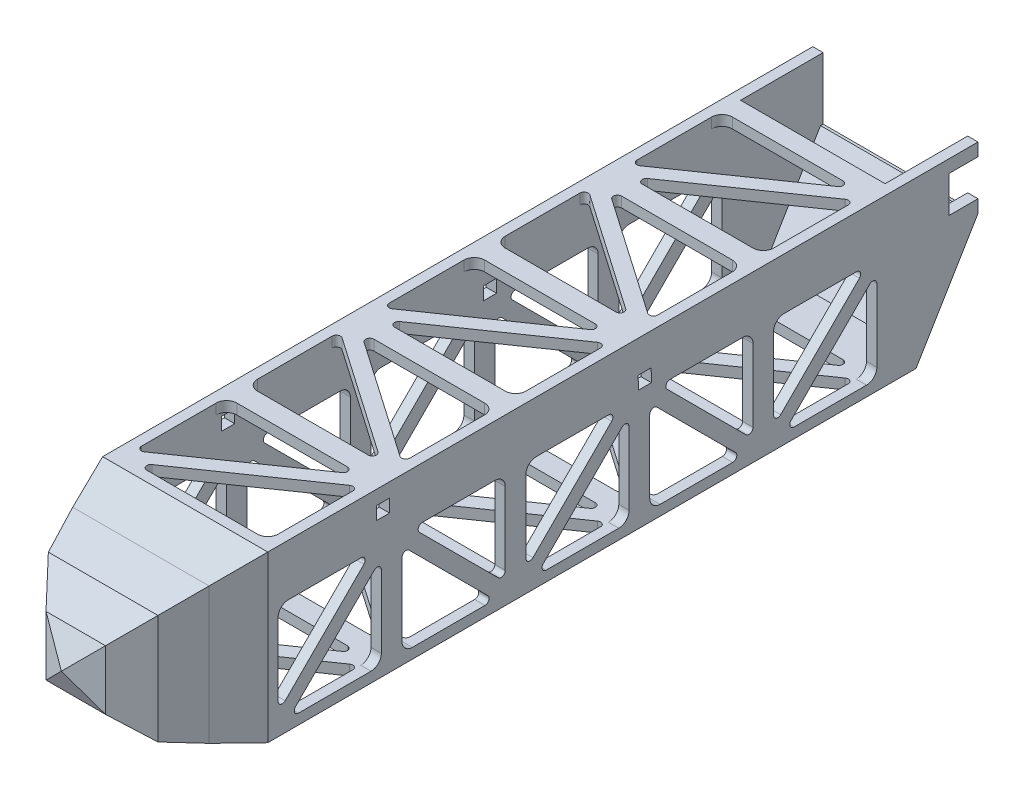
SolidWorks part; units mm, degrees
material "Balsa"
ref_plane "Front Plane" through (0, 0, 0) normal (0, 0, 1) x (1, 0, 0)
ref_plane "Top Plane" through (0, 0, 0) normal (0, 1, 0) x (1, 0, 0)
ref_plane "Right Plane" through (0, 0, 0) normal (1, 0, 0) x (0, 0, -1)
sketch "Sketch1" plane through (0, 0, 0) normal (0, 0, 1) x (1, 0, 0)
  line L1 (-50.8, -50.8) -> (50.8, -50.8)
  line L2 (-50.8, -50.8) -> (-50.8, 50.8)
  line L3 (-50.8, 50.8) -> (50.8, 50.8)
  line L4 (50.8, -50.8) -> (50.8, 50.8)
  line L5 (-50.8, -50.8) -> (50.8, 50.8) construction
  line L6 (-50.8, 50.8) -> (50.8, -50.8) construction
  point P0 (0, 0)
  dimension "D1" = 101.6
extrude "Boss-Extrude1" add sketch "Sketch1" along normal blind 436.88 contours L2 L1 L4 L3
ref_plane "Plane1" through (0, 0, 464.1566) normal (0, 0, 1) x (1, 0, 0)
sketch "Sketch3" plane through (0, 0, 464.1566) normal (0, 0, 1) x (1, 0, 0)
  line L1 (-41.9373, -41.9373) -> (41.9373, -41.9373)
  line L2 (-41.9373, -41.9373) -> (-41.9373, 41.9373)
  line L3 (-41.9373, 41.9373) -> (41.9373, 41.9373)
  line L4 (41.9373, -41.9373) -> (41.9373, 41.9373)
  line L5 (-41.9373, -41.9373) -> (41.9373, 41.9373) construction
  line L6 (-41.9373, 41.9373) -> (41.9373, -41.9373) construction
  point P0 (0, 0)
  dimension "D1" = 83.8746
  dimension "D2" = 83.8746
sketch "Sketch5" plane through (0, 0, 436.88) normal (0, 0, 1) x (1, 0, 0)
  line L0 (50.8, -50.8) -> (50.8, 50.8) construction
  line L1 (-50.8, 50.8) -> (50.8, 50.8) construction
  line L2 (-50.8, -50.8) -> (-50.8, 50.8) construction
  line L3 (-50.8, -50.8) -> (50.8, -50.8) construction
  line L4 (50.8, -50.8) -> (50.8, 50.8)
  line L5 (-50.8, 50.8) -> (50.8, 50.8)
  line L6 (-50.8, -50.8) -> (-50.8, 50.8)
  line L7 (-50.8, -50.8) -> (50.8, -50.8)
  dimension "D1" = 101.6
  dimension "D2" = 101.6
loft "Loft2" add profiles "Sketch5", "Sketch3" connector at (-50.8, 50.8, 436.88) connector at (-41.9373, 41.9373, 464.1566)
ref_plane "Plane2" through (0, 0, 487.3594) normal (0, 0, 1) x (1, 0, 0)
sketch "Sketch6" plane through (0, 0, 487.3594) normal (0, 0, 1) x (1, 0, 0)
  line L1 (-33.716, -33.716) -> (33.716, -33.716)
  line L2 (-33.716, -33.716) -> (-33.716, 33.716)
  line L3 (-33.716, 33.716) -> (33.716, 33.716)
  line L4 (33.716, -33.716) -> (33.716, 33.716)
  line L5 (-33.716, -33.716) -> (33.716, 33.716) construction
  line L6 (-33.716, 33.716) -> (33.716, -33.716) construction
  point P0 (0, 0)
loft "Loft3" add profiles "Sketch3<6>", "Sketch6" connector at (-41.9373, 41.9373, 464.1566) connector at (-33.716, 33.716, 487.3594)
sketch "Sketch3<6>" plane through (0, 0, 464.1566) normal (0, 0, 1) x (1, 0, 0) same geometry as "Sketch3"
ref_plane "Plane3" through (0, 0, 504.2173) normal (0, 0, 1) x (1, 0, 0)
sketch "Sketch7" plane through (0, 0, 504.2173) normal (0, 0, 1) x (1, 0, 0)
  line L5 (-41.9373, -41.9373) -> (41.9373, 41.9373) construction
  line L6 (-18.3041, -18.3041) -> (18.3041, -18.3041)
  line L8 (-18.3041, -18.3041) -> (-18.3041, 18.3041)
  line L9 (-18.3041, 18.3041) -> (18.3041, 18.3041)
  line L10 (18.3041, -18.3041) -> (18.3041, 18.3041)
  line L11 (-18.3041, -18.3041) -> (18.3041, 18.3041) construction
  line L12 (-18.3041, 18.3041) -> (18.3041, -18.3041) construction
  point P1 (0, 0)
loft "Loft4" add profiles "Sketch6<4>", "Sketch7" connector at (33.716, 33.716, 487.3594) connector at (18.3041, 18.3041, 504.2173)
sketch "Sketch6<4>" plane through (0, 0, 487.3594) normal (0, 0, 1) x (1, 0, 0) same geometry as "Sketch6"
sketch3d "3DSketch1" plane through (0, 0, 0) normal (0, 0, 1) x (1, 0, 0)
  dimension "D1" = 8.8627
sketch "Sketch8" plane through (0, 0, 513.08) normal (0, 0, 1) x (1, 0, 0)
  point P0 (0, 0)
loft "Loft5" add profiles "Sketch8", "Sketch7<5>"
sketch "Sketch7<5>" plane through (0, 0, 504.2173) normal (0, 0, 1) x (1, 0, 0) same geometry as "Sketch7"
shell "Shell1" thickness 6.35 removed face at (0, 0, 0)
sketch "Sketch10" plane through (50.8, 0, 0) normal (1, 0, 0) x (0, 0, -1)
  line L0 (-436.88, 50.8) -> (0, 50.8) construction
  line L3 (0, 50.8) -> (-68.9584, 50.8)
  line L4 (-68.9584, -50.8) -> (-68.9584, 50.8)
  line L5 (0, 50.8) -> (0, 12.7)
  line L6 (0, -50.8) -> (-38.1, -50.8)
  line L7 (0, 12.7) -> (-38.1, -50.8)
  line L8 (0, 12.7) -> (0, -50.8)
  line M16 (0, -50.8) -> (0, 50.8)
  line M19 (-436.88, -50.8) -> (0, -50.8)
  dimension "D1" = 38.1
  dimension "D2" = 38.1
  dimension "D3" = 63.5
extrude "Cut-Extrude2" cut sketch "Sketch10" against normal through all contours L7 M16 M19 region at (50.8, -29.6333, 12.7)
sketch "Sketch11" plane through (50.8, 0, 0) normal (1, 0, 0) x (0, 0, -1)
  line L0 (-38.1, -50.8) -> (-39.6875, -50.8)
  line L1 (-436.88, -50.8) -> (-38.1, -50.8) construction
  line L2 (0, 50.8) -> (-1.5875, 50.8)
  line L3 (-436.88, 50.8) -> (0, 50.8) construction
  line L4 (-1.5875, 50.8) -> (-1.5875, 12.7)
  line L5 (0, 50.8) -> (0, 12.7)
  line L6 (-1.5875, 12.7) -> (-39.6875, -50.8)
  line L7 (0, 12.7) -> (-38.1, -50.8)
  dimension "D1" = 1.5875
  dimension "D2" = 1.5875
extrude "Boss-Extrude2" add sketch "Sketch11" against normal blind 101.6
sketch "Sketch12" plane through (0, 0, 0) normal (0, 0, -1) x (-1, 0, 0)
  line L0 (-50.8, 50.8) -> (-44.45, 50.8)
  line L1 (50.8, 50.8) -> (-50.8, 50.8) construction
  line L2 (50.8, 12.7) -> (-50.8, 12.7) construction
  line L3 (-44.45, 50.8) -> (44.45, 50.8)
  line L4 (-44.45, 50.8) -> (-44.45, 12.7)
  line L5 (-44.45, 12.7) -> (44.45, 12.7)
  line L6 (44.45, 50.8) -> (44.45, 12.7)
  line M7 (-50.8, 12.7) -> (50.8, 12.7)
  line M9 (50.8, 50.8) -> (-50.8, 50.8)
  dimension "D1" = 6.35
  dimension "D2" = 88.9
extrude "Cut-Extrude3" cut sketch "Sketch12" against normal blind 50.8 contours L6 L4 M9 M7 region at (0, 31.75, 0)
sketch "Sketch15" plane through (50.8, 0, 0) normal (1, 0, 0) x (0, 0, -1)
  line L0 (0, 12.7) -> (0, 50.8) construction
  line L1 (0, 42.926) -> (-17.78, 42.926)
  line L2 (0, 42.926) -> (0, 20.574)
  line L3 (0, 20.574) -> (-17.78, 20.574)
  line L4 (-17.78, 42.926) -> (-17.78, 20.574)
  line L5 (-436.88, 50.8) -> (0, 50.8) construction
  dimension "D1" = 17.78
  dimension "D2" = 22.352
  dimension "D3" = 7.874
extrude "Cut-Extrude5" cut sketch "Sketch15" against normal up to surface (6.35 mm away)
sketch "Sketch16" plane through (50.8, 0, 0) normal (1, 0, 0) x (0, 0, -1)
  line L0 (-436.88, -50.8) -> (-436.88, 50.8) construction
  line L1 (-424.18, 19.05) -> (-379.5121, 19.05)
  line L2 (-430.53, 12.7) -> (-430.53, -31.9679)
  line L3 (-418.0479, -44.45) -> (-373.38, -44.45)
  line L4 (-367.03, 6.5679) -> (-367.03, -38.1)
  line L5 (-436.88, -50.8) -> (-38.1, -50.8) construction
  line L6 (-354.33, 6.5679) -> (-354.33, -38.1)
  line L7 (-341.8479, 19.05) -> (-297.18, 19.05)
  line L8 (-290.83, 12.7) -> (-290.83, -31.9679)
  line L9 (-347.98, -44.45) -> (-303.3121, -44.45)
  line L10 (-278.13, 12.7) -> (-278.13, -31.9679)
  line L11 (-271.78, 19.05) -> (-227.1121, 19.05)
  line L12 (-214.63, 6.5679) -> (-214.63, -38.1)
  line L13 (-265.6479, -44.45) -> (-220.98, -44.45)
  line L14 (-201.93, 6.5679) -> (-201.93, -38.1)
  line L15 (-189.4479, 19.05) -> (-144.78, 19.05)
  line L16 (-138.43, 12.7) -> (-138.43, -31.9679)
  line L17 (-195.58, -44.45) -> (-150.9121, -44.45)
  line L18 (-125.73, 12.7) -> (-125.73, -31.9679)
  line L19 (-119.38, 19.05) -> (-74.7121, 19.05)
  line L20 (-62.23, 6.5679) -> (-62.23, -38.1)
  line L21 (-113.2479, -44.45) -> (-68.58, -44.45)
  line L22 (-377.7161, 14.7139) -> (-426.1939, -33.7639)
  line L23 (-419.8439, -40.1139) -> (-371.3661, 8.3639)
  line L24 (-349.9939, 8.3639) -> (-301.5161, -40.1139)
  line L25 (-343.6439, 14.7139) -> (-295.1661, -33.7639)
  line L26 (-273.7939, -33.7639) -> (-225.3161, 14.7139)
  line L27 (-218.9661, 8.3639) -> (-267.4439, -40.1139)
  line L28 (-197.5939, 8.3639) -> (-149.1161, -40.1139)
  line L29 (-142.7661, -33.7639) -> (-191.2439, 14.7139)
  line L30 (-121.3939, -33.7639) -> (-72.9161, 14.7139)
  line L31 (-66.5661, 8.3639) -> (-115.0439, -40.1139)
  arc A0 (-430.53, -38.1) -> (-424.18, -44.45) centre (-424.18, -38.1) ccw
  arc A1 (-373.38, -44.45) -> (-367.03, -38.1) centre (-373.38, -38.1) ccw
  arc A2 (-373.38, 19.05) -> (-367.03, 12.7) centre (-373.38, 12.7) cw
  arc A3 (-424.18, 19.05) -> (-430.53, 12.7) centre (-424.18, 12.7) ccw
  arc A4 (-347.98, 19.05) -> (-354.33, 12.7) centre (-347.98, 12.7) ccw
  arc A5 (-354.33, -38.1) -> (-347.98, -44.45) centre (-347.98, -38.1) ccw
  arc A6 (-297.18, 19.05) -> (-290.83, 12.7) centre (-297.18, 12.7) cw
  arc A7 (-297.18, -44.45) -> (-290.83, -38.1) centre (-297.18, -38.1) ccw
  arc A8 (-271.78, 19.05) -> (-278.13, 12.7) centre (-271.78, 12.7) ccw
  arc A9 (-278.13, -38.1) -> (-271.78, -44.45) centre (-271.78, -38.1) ccw
  arc A10 (-220.98, 19.05) -> (-214.63, 12.7) centre (-220.98, 12.7) cw
  arc A11 (-220.98, -44.45) -> (-214.63, -38.1) centre (-220.98, -38.1) ccw
  arc A12 (-195.58, 19.05) -> (-201.93, 12.7) centre (-195.58, 12.7) ccw
  arc A13 (-201.93, -38.1) -> (-195.58, -44.45) centre (-195.58, -38.1) ccw
  arc A14 (-144.78, 19.05) -> (-138.43, 12.7) centre (-144.78, 12.7) cw
  arc A15 (-144.78, -44.45) -> (-138.43, -38.1) centre (-144.78, -38.1) ccw
  arc A16 (-119.38, 19.05) -> (-125.73, 12.7) centre (-119.38, 12.7) ccw
  arc A17 (-125.73, -38.1) -> (-119.38, -44.45) centre (-119.38, -38.1) ccw
  arc A18 (-68.58, 19.05) -> (-62.23, 12.7) centre (-68.58, 12.7) cw
  arc A19 (-68.58, -44.45) -> (-62.23, -38.1) centre (-68.58, -38.1) ccw
  arc A20 (-74.7121, 19.05) -> (-72.9161, 14.7139) centre (-74.7121, 16.51) cw
  arc A21 (-66.5661, 8.3639) -> (-62.23, 6.5679) centre (-64.77, 6.5679) cw
  arc A22 (-115.0439, -40.1139) -> (-113.2479, -44.45) centre (-113.2479, -41.91) ccw
  arc A23 (-121.3939, -33.7639) -> (-125.73, -31.9679) centre (-123.19, -31.9679) cw
  arc A24 (-150.9121, -44.45) -> (-149.1161, -40.1139) centre (-150.9121, -41.91) ccw
  arc A25 (-142.7661, -33.7639) -> (-138.43, -31.9679) centre (-140.97, -31.9679) ccw
  arc A26 (-189.4479, 19.05) -> (-191.2439, 14.7139) centre (-189.4479, 16.51) ccw
  arc A27 (-197.5939, 8.3639) -> (-201.93, 6.5679) centre (-199.39, 6.5679) ccw
  arc A28 (-227.1121, 19.05) -> (-225.3161, 14.7139) centre (-227.1121, 16.51) cw
  arc A29 (-218.9661, 8.3639) -> (-214.63, 6.5679) centre (-217.17, 6.5679) cw
  arc A30 (-265.6479, -44.45) -> (-267.4439, -40.1139) centre (-265.6479, -41.91) cw
  arc A31 (-278.13, -31.9679) -> (-273.7939, -33.7639) centre (-275.59, -31.9679) ccw
  arc A32 (-303.3121, -44.45) -> (-301.5161, -40.1139) centre (-303.3121, -41.91) ccw
  arc A33 (-290.83, -31.9679) -> (-295.1661, -33.7639) centre (-293.37, -31.9679) cw
  arc A34 (-341.8479, 19.05) -> (-343.6439, 14.7139) centre (-341.8479, 16.51) ccw
  arc A35 (-349.9939, 8.3639) -> (-354.33, 6.5679) centre (-351.79, 6.5679) ccw
  arc A36 (-367.03, 6.5679) -> (-371.3661, 8.3639) centre (-369.57, 6.5679) ccw
  arc A37 (-418.0479, -44.45) -> (-419.8439, -40.1139) centre (-418.0479, -41.91) cw
  arc A38 (-377.7161, 14.7139) -> (-379.5121, 19.05) centre (-379.5121, 16.51) ccw
  arc A39 (-426.1939, -33.7639) -> (-430.53, -31.9679) centre (-427.99, -31.9679) cw
  point P12 (-367.03, -44.45)
  point P15 (-367.03, 19.05)
  point P18 (-430.53, 19.05)
  dimension "D1" = 6.35
  dimension "D5" = 6.35
  dimension "D7" = 2.54
  dimension "D2" = 6.35
  dimension "D3" = 63.5
  dimension "D4" = 63.5
  dimension "D6" = 5
extrude "Cut-Extrude6" cut sketch "Sketch16" against normal up to surface (101.6 mm away) contours L1 A3 L2 L22 | L3 A1 L4 L23 | L6 A5 L9 L24 | A6 L7 L25 L8 | L11 A8 L10 L26 | L13 A11 L12 L27 | L14 A13 L17 L28 | A14 L15 L29 L16 | L21 A19 L20 L31 | L19 A16 L18 L30 region at (50.8, -0.0083, 411.4717) region at (50.8, -25.3917, 386.0883) region at (50.8, -25.3917, 335.2717) region at (50.8, -0.0083, 309.8883) region at (50.8, -0.0083, 259.0717) region at (50.8, -25.3917, 233.6883) region at (50.8, -25.3917, 182.8717) region at (50.8, -0.0083, 157.4883) region at (50.8, -0.0083, 106.6717) region at (50.8, -25.3917, 81.2883) up to face at (-50.8, 2.54, 182.372)
sketch "Sketch17" plane through (0, 50.8, 0) normal (0, 1, 0) x (1, 0, 0)
  line L0 (50.8, -436.88) -> (50.8, 0) construction
  line L1 (38.1, -430.53) -> (-22.2093, -430.53)
  line L2 (44.45, -424.18) -> (44.45, -382.8539)
  line L3 (22.2093, -367.03) -> (-38.1, -367.03)
  line L4 (-44.45, -414.7061) -> (-44.45, -373.38)
  line L5 (-50.8, -436.88) -> (50.8, -436.88) construction
  line L6 (-50.8, -436.88) -> (-50.8, 0) construction
  line L7 (44.45, -344.747) -> (44.45, -303.4209)
  line L8 (22.2093, -360.5709) -> (-38.1, -360.5709)
  line L9 (-44.45, -354.2209) -> (-44.45, -306.6045)
  line L11 (44.45, -284.2618) -> (44.45, -236.6454)
  line L12 (38.1, -290.6118) -> (-32.7601, -290.6118)
  line L13 (-44.45, -281.0782) -> (-44.45, -233.4618)
  line L14 (37.5789, -227.1118) -> (-38.1, -227.1118)
  line L15 (44.45, -211.1191) -> (44.45, -163.5027)
  line L16 (32.7601, -220.6527) -> (-38.1, -220.6527)
  line L17 (-44.45, -214.3027) -> (-44.45, -166.6863)
  line L19 (44.45, -144.3436) -> (44.45, -98.3913)
  line L20 (38.1, -150.6936) -> (-37.3066, -150.6936)
  line L21 (-44.45, -139.4958) -> (-44.45, -93.5436)
  line L22 (29.9688, -87.1936) -> (-38.1, -87.1936)
  line L23 (-36.6606, -418.7874) -> (25.0348, -376.0751)
  line L24 (38.1, -367.03) -> (44.45, -373.38)
  line L25 (-25.0348, -421.4849) -> (36.6606, -378.7726)
  line L26 (36.6606, -348.8283) -> (-31.4146, -301.6993)
  line L27 (-41.8325, -305.233) -> (25.0348, -351.5257)
  line L28 (-33.7096, -287.5723) -> (41.8325, -235.2739)
  line L29 (38.5284, -226.8152) -> (-41.8325, -282.4497)
  line L30 (33.7096, -217.6132) -> (-41.8325, -165.3148)
  line L31 (-31.4146, -161.7811) -> (41.8325, -212.4906)
  line L32 (-38.7524, -151.1452) -> (40.4642, -96.303)
  line L33 (31.4146, -91.822) -> (-40.4642, -141.5842)
  line L35 (38.1, -157.1527) -> (-37.3066, -157.1527) [skipped]
  line L36 (38.1, -157.1527) -> (35.6588, -123.3001)
  line L37 (-29.9688, -157.1527) -> (38.1, -157.1527)
  line L38 (-29.9688, -297.0709) -> (38.1, -297.0709)
  line L39 (38.1, -297.0709) -> (-36.5494, -297.0709) [skipped]
  arc A0 (44.45, -373.38) -> (38.1, -367.03) centre (38.1, -373.38) ccw
  arc A1 (38.1, -430.53) -> (44.45, -424.18) centre (38.1, -424.18) ccw
  arc A2 (-38.1, -430.53) -> (-44.45, -424.18) centre (-38.1, -424.18) cw
  arc A3 (-38.1, -367.03) -> (-44.45, -373.38) centre (-38.1, -373.38) ccw
  arc A4 (38.1, -360.5709) -> (44.45, -354.2209) centre (38.1, -354.2209) ccw
  arc A5 (44.45, -303.4209) -> (38.1, -297.0709) centre (38.1, -303.4209) ccw
  arc A6 (-38.1, -360.5709) -> (-44.45, -354.2209) centre (-38.1, -354.2209) cw
  arc A7 (-38.1, -297.0709) -> (-44.45, -303.4209) centre (-38.1, -303.4209) ccw
  arc A8 (38.1, -290.6118) -> (44.45, -284.2618) centre (38.1, -284.2618) ccw
  arc A9 (44.45, -233.4618) -> (38.1, -227.1118) centre (38.1, -233.4618) ccw
  arc A10 (-38.1, -290.6118) -> (-44.45, -284.2618) centre (-38.1, -284.2618) cw
  arc A11 (-38.1, -227.1118) -> (-44.45, -233.4618) centre (-38.1, -233.4618) ccw
  arc A12 (38.1, -220.6527) -> (44.45, -214.3027) centre (38.1, -214.3027) ccw
  arc A13 (44.45, -163.5027) -> (38.1, -157.1527) centre (38.1, -163.5027) ccw
  arc A14 (-38.1, -220.6527) -> (-44.45, -214.3027) centre (-38.1, -214.3027) cw
  arc A16 (38.1, -150.6936) -> (44.45, -144.3436) centre (38.1, -144.3436) ccw
  arc A17 (44.45, -93.5436) -> (38.1, -87.1936) centre (38.1, -93.5436) ccw
  arc A18 (-38.1, -150.6936) -> (-44.45, -144.3436) centre (-38.1, -144.3436) cw
  arc A19 (-38.1, -87.1936) -> (-44.45, -93.5436) centre (-38.1, -93.5436) ccw
  arc A20 (-40.4642, -141.5842) -> (-44.45, -139.4958) centre (-41.91, -139.4958) cw
  arc A21 (31.4146, -91.822) -> (29.9688, -87.1936) centre (29.9688, -89.7336) ccw
  arc A22 (40.4642, -96.303) -> (44.45, -98.3913) centre (41.91, -98.3913) cw
  arc A23 (-38.7524, -151.1452) -> (-37.3066, -150.6936) centre (-37.3066, -153.2336) ccw
  arc A25 (-41.8325, -165.3148) -> (-44.45, -166.6863) centre (-42.7819, -166.6863) ccw
  arc A26 (44.45, -211.1191) -> (41.8325, -212.4906) centre (42.7819, -211.1191) cw
  arc A27 (33.7096, -217.6132) -> (32.7601, -220.6527) centre (32.7601, -218.9846) cw
  arc A28 (37.5789, -227.1118) -> (38.5284, -226.8152) centre (37.5789, -225.4437) cw
  arc A29 (41.8325, -235.2739) -> (44.45, -236.6454) centre (42.7819, -236.6454) cw
  arc A30 (-32.7601, -290.6118) -> (-33.7096, -287.5723) centre (-32.7601, -288.9437) cw
  arc A31 (-41.8325, -282.4497) -> (-44.45, -281.0782) centre (-42.7819, -281.0782) cw
  arc A32 (-44.45, -306.6045) -> (-41.8325, -305.233) centre (-42.7819, -306.6045) cw
  arc A34 (44.45, -344.747) -> (36.6606, -348.8283) centre (39.4861, -344.747) cw
  arc A35 (22.2093, -360.5709) -> (25.0348, -351.5257) centre (22.2093, -355.607) ccw
  arc A36 (44.45, -382.8539) -> (36.6606, -378.7726) centre (39.4861, -382.8539) ccw
  arc A37 (25.0348, -376.0751) -> (22.2093, -367.03) centre (22.2093, -371.9939) ccw
  arc A38 (-44.45, -414.7061) -> (-36.6606, -418.7874) centre (-39.4861, -414.7061) ccw
  arc A39 (-22.2093, -430.53) -> (-25.0348, -421.4849) centre (-22.2093, -425.5661) cw
  arc A40 (-38.1, -157.1527) -> (-44.45, -163.5027) centre (-38.1, -163.5027) ccw [skipped]
  arc A41 (-31.4146, -161.7811) -> (-29.9688, -157.1527) centre (-29.9688, -159.6927) cw
  arc A42 (-31.4146, -301.6993) -> (-29.9688, -297.0709) centre (-29.9688, -299.6109) cw
  point P16 (-44.45, -430.53)
  point P19 (-44.45, -367.03)
  dimension "D1" = 6.35
  dimension "D5" = 6.35
  dimension "D7" = 2.54
  dimension "D2" = 6.35
  dimension "D4" = 63.5
  dimension "D6" = 5
  dimension "D8" = 2.54
  dimension "D9" = 2.54
  dimension "D3" = 6.35
sketch "Sketch18" plane through (0, 50.8, 0) normal (0, 1, 0) x (1, 0, 0)
  line L0 (-50.8, -436.88) -> (-50.8, 0) construction
  line L1 (38.1, -430.53) -> (-29.9688, -430.53)
  line L2 (44.45, -424.18) -> (44.45, -378.2278)
  line L3 (29.9688, -367.03) -> (-38.1, -367.03)
  line L4 (-44.45, -419.3322) -> (-44.45, -373.38)
  line L5 (50.8, -436.88) -> (50.8, 0) construction
  line L6 (-50.8, -436.88) -> (50.8, -436.88) construction
  line L7 (-40.4642, -299.9394) -> (31.4146, -349.7016)
  line L8 (-38.1, -354.33) -> (29.9688, -354.33)
  line L9 (-44.45, -347.98) -> (-44.45, -302.0278)
  line L10 (-29.9688, -290.83) -> (38.1, -290.83)
  line L11 (44.45, -343.1322) -> (44.45, -297.18)
  line L12 (40.4642, -345.2206) -> (-31.4146, -295.4584)
  line L13 (31.4146, -371.6584) -> (-40.4642, -421.4206)
  line L14 (-31.4146, -425.9016) -> (40.4642, -376.1394)
  line L15 (38.1, -278.13) -> (-29.9688, -278.13)
  line L16 (44.45, -271.78) -> (44.45, -225.8278)
  line L17 (-31.4146, -273.5016) -> (40.4642, -223.7394)
  line L18 (31.4146, -219.2584) -> (-40.4642, -269.0206)
  line L19 (29.9688, -214.63) -> (-38.1, -214.63)
  line L20 (-44.45, -266.9322) -> (-44.45, -220.98)
  line L21 (-38.1, -201.93) -> (29.9688, -201.93)
  line L22 (-44.45, -195.58) -> (-44.45, -149.6278)
  line L23 (-40.4642, -147.5394) -> (31.4146, -197.3016)
  line L24 (40.4642, -192.8206) -> (-31.4146, -143.0584)
  line L25 (-29.9688, -138.43) -> (38.1, -138.43)
  line L26 (44.45, -190.7322) -> (44.45, -144.78)
  line L27 (38.1, -125.73) -> (-29.9688, -125.73)
  line L28 (44.45, -119.38) -> (44.45, -73.4278)
  line L29 (-31.4146, -121.1016) -> (40.4642, -71.3394)
  line L30 (31.4146, -66.8584) -> (-40.4642, -116.6206)
  line L31 (29.9688, -62.23) -> (-38.1, -62.23)
  line L32 (-44.45, -114.5322) -> (-44.45, -68.58)
  line L39 (-38.1, -49.53) -> (29.9688, -49.53) [skipped]
  line L40 (-40.4642, 4.8606) -> (31.4146, -44.9016) [skipped]
  line L41 (-44.45, -43.18) -> (-44.45, 2.7722) [skipped]
  line L42 (40.4642, -40.4206) -> (-31.4146, 9.3416) [skipped]
  line L43 (-29.9688, 13.97) -> (38.1, 13.97) [skipped]
  line L44 (44.45, -38.3322) -> (44.45, 7.62) [skipped]
  arc A0 (38.1, -430.53) -> (44.45, -424.18) centre (38.1, -424.18) ccw
  arc A3 (-38.1, -367.03) -> (-44.45, -373.38) centre (-38.1, -373.38) ccw
  arc A4 (-38.1, -354.33) -> (-44.45, -347.98) centre (-38.1, -347.98) cw
  arc A6 (38.1, -290.83) -> (44.45, -297.18) centre (38.1, -297.18) cw
  arc A8 (44.45, -343.1322) -> (40.4642, -345.2206) centre (41.91, -343.1322) cw
  arc A9 (-29.9688, -290.83) -> (-31.4146, -295.4584) centre (-29.9688, -293.37) ccw
  arc A10 (-44.45, -302.0278) -> (-40.4642, -299.9394) centre (-41.91, -302.0278) cw
  arc A11 (29.9688, -354.33) -> (31.4146, -349.7016) centre (29.9688, -351.79) ccw
  arc A12 (44.45, -378.2278) -> (40.4642, -376.1394) centre (41.91, -378.2278) ccw
  arc A13 (29.9688, -367.03) -> (31.4146, -371.6584) centre (29.9688, -369.57) cw
  arc A14 (-29.9688, -430.53) -> (-31.4146, -425.9016) centre (-29.9688, -427.99) cw
  arc A15 (-44.45, -419.3322) -> (-40.4642, -421.4206) centre (-41.91, -419.3322) ccw
  arc A16 (-29.9688, -278.13) -> (-31.4146, -273.5016) centre (-29.9688, -275.59) cw
  arc A17 (38.1, -278.13) -> (44.45, -271.78) centre (38.1, -271.78) ccw
  arc A18 (44.45, -225.8278) -> (40.4642, -223.7394) centre (41.91, -225.8278) ccw
  arc A19 (-44.45, -266.9322) -> (-40.4642, -269.0206) centre (-41.91, -266.9322) ccw
  arc A20 (29.9688, -214.63) -> (31.4146, -219.2584) centre (29.9688, -217.17) cw
  arc A21 (-38.1, -214.63) -> (-44.45, -220.98) centre (-38.1, -220.98) ccw
  arc A22 (29.9688, -201.93) -> (31.4146, -197.3016) centre (29.9688, -199.39) ccw
  arc A23 (-38.1, -201.93) -> (-44.45, -195.58) centre (-38.1, -195.58) cw
  arc A24 (-44.45, -149.6278) -> (-40.4642, -147.5394) centre (-41.91, -149.6278) cw
  arc A25 (-29.9688, -138.43) -> (-31.4146, -143.0584) centre (-29.9688, -140.97) ccw
  arc A26 (44.45, -190.7322) -> (40.4642, -192.8206) centre (41.91, -190.7322) cw
  arc A27 (38.1, -138.43) -> (44.45, -144.78) centre (38.1, -144.78) cw
  arc A28 (-29.9688, -125.73) -> (-31.4146, -121.1016) centre (-29.9688, -123.19) cw
  arc A29 (38.1, -125.73) -> (44.45, -119.38) centre (38.1, -119.38) ccw
  arc A30 (44.45, -73.4278) -> (40.4642, -71.3394) centre (41.91, -73.4278) ccw
  arc A31 (-44.45, -114.5322) -> (-40.4642, -116.6206) centre (-41.91, -114.5322) ccw
  arc A32 (29.9688, -62.23) -> (31.4146, -66.8584) centre (29.9688, -64.77) cw
  arc A33 (-38.1, -62.23) -> (-44.45, -68.58) centre (-38.1, -68.58) ccw
  arc A40 (29.9688, -49.53) -> (31.4146, -44.9016) centre (29.9688, -46.99) ccw [skipped]
  arc A41 (-44.45, 2.7722) -> (-40.4642, 4.8606) centre (-41.91, 2.7722) cw [skipped]
  arc A42 (-38.1, -49.53) -> (-44.45, -43.18) centre (-38.1, -43.18) cw [skipped]
  arc A43 (-29.9688, 13.97) -> (-31.4146, 9.3416) centre (-29.9688, 11.43) ccw [skipped]
  arc A44 (38.1, 13.97) -> (44.45, 7.62) centre (38.1, 7.62) cw [skipped]
  arc A45 (44.45, -38.3322) -> (40.4642, -40.4206) centre (41.91, -38.3322) cw [skipped]
  point P12 (44.45, -430.53)
  point P15 (44.45, -367.03)
  point P28 (44.45, -354.33)
  point P31 (44.45, -290.83)
  dimension "D1" = 6.35
  dimension "D5" = 6.35
  dimension "D2" = 6.35
  dimension "D4" = 63.5
  dimension "D3" = 6.35
  dimension "D10" = 6.35
  dimension "D11" = 2.54
  dimension "D6" = 12.7
  dimension "D8" = 6.35
  dimension "D9" = 6.35
  dimension "D12" = 3
extrude "Cut-Extrude9" cut sketch "Sketch18" against normal up to surface (101.6 mm away) up to face at (0, -50.8, 237.49)
ref_plane "Plane4" through (0, 38.1, 0) normal (0, 1, 0) x (1, 0, 0)
ref_plane "Plane5" through (0, -4.6068, 436.295) normal (0, -0.0106, 0.9999) x (1, 0, 0)
sketch "Sketch19" plane through (-50.8, 0, 0) normal (-1, 0, 0) x (0, 0, 1)
  line L0 (361.9883, 34.0995) -> (361.9883, 42.1005)
  line L1 (361.9883, 34.0995) -> (361.9883, 42.1005)
  line L2 (361.9883, 42.1005) -> (369.9893, 42.1005)
  line L3 (361.9883, 42.1005) -> (369.9893, 42.1005)
  line L4 (369.9893, 42.1005) -> (369.9893, 34.0995)
  line L5 (369.9893, 42.1005) -> (369.9893, 34.0995)
  line L6 (369.9893, 34.0995) -> (361.9883, 34.0995)
  line L7 (369.9893, 34.0995) -> (361.9883, 34.0995)
  line L8 (200.9418, 23.0654) -> (201.0263, 31.066)
  line L9 (200.9418, 23.0654) -> (201.0263, 31.066)
  line L10 (201.0263, 31.066) -> (209.0268, 30.9815)
  line L11 (201.0263, 31.066) -> (209.0268, 30.9815)
  line L12 (209.0268, 30.9815) -> (208.9424, 22.9809)
  line L13 (209.0268, 30.9815) -> (208.9424, 22.9809)
  line L14 (208.9424, 22.9809) -> (200.9418, 23.0654)
  line L15 (208.9424, 22.9809) -> (200.9418, 23.0654)
extrude "Cut-Extrude10" cut sketch "Sketch19" against normal through all
sketch "Sketch20" plane through (50.8, 0, 0) normal (1, 0, 0) x (0, 0, -1)
  line L0 (-189.4479, 19.05) -> (-144.78, 19.05) construction
  line L1 (-142.7661, -33.7639) -> (-191.2439, 14.7139) construction
  line L2 (-138.43, 12.7) -> (-138.43, -31.9679) construction
  line L3 (-125.73, 12.7) -> (-125.73, -31.9679) construction
  line L4 (-119.38, 19.05) -> (-74.7121, 19.05) construction
  line L5 (-121.3939, -33.7639) -> (-72.9161, 14.7139) construction
  line L6 (-62.23, 6.5679) -> (-62.23, -38.1) construction
  line L7 (-113.2479, -44.45) -> (-68.58, -44.45) construction
  line L8 (-66.5661, 8.3639) -> (-115.0439, -40.1139) construction
  line L9 (-17.78, 20.574) -> (-17.78, 42.926)
  line L10 (-17.78, 42.926) -> (0, 42.926)
  line L11 (0, 42.926) -> (0, 50.8)
  line L12 (0, 50.8) -> (-436.88, 50.8)
  line L13 (-436.88, 50.8) -> (-436.88, -50.8)
  line L14 (-436.88, -50.8) -> (-38.1, -50.8)
  line L15 (-38.1, -50.8) -> (0, 12.7)
  line L16 (0, 12.7) -> (0, 20.574)
  line L17 (0, 20.574) -> (-17.78, 20.574)
  line L18 (-17.78, 20.574) -> (-17.78, 42.926)
  line L19 (-17.78, 42.926) -> (0, 42.926)
  line L20 (0, 42.926) -> (0, 50.8)
  line L21 (0, 50.8) -> (-436.88, 50.8)
  line L22 (-436.88, 50.8) -> (-436.88, -50.8)
  line L23 (-436.88, -50.8) -> (-38.1, -50.8)
  line L24 (-38.1, -50.8) -> (0, 12.7)
  line L25 (0, 12.7) -> (0, 20.574)
  line L26 (0, 20.574) -> (-17.78, 20.574)
  line L27 (-197.5939, 8.3639) -> (-149.1161, -40.1139) construction
  line L28 (-195.58, -44.45) -> (-150.9121, -44.45) construction
  line L29 (-201.93, 6.5679) -> (-201.93, -38.1) construction
  line L30 (-214.63, 6.5679) -> (-214.63, -38.1) construction
  line L31 (-265.6479, -44.45) -> (-220.98, -44.45) construction
  line L32 (-218.9661, 8.3639) -> (-267.4439, -40.1139) construction
  line L33 (-273.7939, -33.7639) -> (-225.3161, 14.7139) construction
  line L34 (-271.78, 19.05) -> (-227.1121, 19.05) construction
  line L35 (-278.13, 12.7) -> (-278.13, -31.9679) construction
  line L36 (-341.8479, 19.05) -> (-297.18, 19.05) construction
  line L37 (-290.83, 12.7) -> (-290.83, -31.9679) construction
  line L38 (-343.6439, 14.7139) -> (-295.1661, -33.7639) construction
  line L39 (-347.98, -44.45) -> (-303.3121, -44.45) construction
  line L40 (-349.9939, 8.3639) -> (-301.5161, -40.1139) construction
  line L41 (-354.33, 6.5679) -> (-354.33, -38.1) construction
  line L42 (-367.03, 6.5679) -> (-367.03, -38.1) construction
  line L43 (-418.0479, -44.45) -> (-373.38, -44.45) construction
  line L44 (-419.8439, -40.1139) -> (-371.3661, 8.3639) construction
  line L45 (-377.7161, 14.7139) -> (-426.1939, -33.7639) construction
  line L46 (-430.53, 12.7) -> (-430.53, -31.9679) construction
  line L47 (-424.18, 19.05) -> (-379.5121, 19.05) construction
  line L48 (-189.4479, 19.05) -> (-144.78, 19.05)
  line L49 (-142.7661, -33.7639) -> (-191.2439, 14.7139)
  line L50 (-138.43, 12.7) -> (-138.43, -31.9679)
  line L51 (-125.73, 12.7) -> (-125.73, -31.9679)
  line L52 (-119.38, 19.05) -> (-74.7121, 19.05)
  line L53 (-121.3939, -33.7639) -> (-72.9161, 14.7139)
  line L54 (-62.23, 6.5679) -> (-62.23, -38.1)
  line L55 (-113.2479, -44.45) -> (-68.58, -44.45)
  line L56 (-66.5661, 8.3639) -> (-115.0439, -40.1139)
  line L57 (-197.5939, 8.3639) -> (-149.1161, -40.1139)
  line L58 (-195.58, -44.45) -> (-150.9121, -44.45)
  line L59 (-201.93, 6.5679) -> (-201.93, -38.1)
  line L60 (-214.63, 6.5679) -> (-214.63, -38.1)
  line L61 (-265.6479, -44.45) -> (-220.98, -44.45)
  line L62 (-218.9661, 8.3639) -> (-267.4439, -40.1139)
  line L63 (-273.7939, -33.7639) -> (-225.3161, 14.7139)
  line L64 (-271.78, 19.05) -> (-227.1121, 19.05)
  line L65 (-278.13, 12.7) -> (-278.13, -31.9679)
  line L66 (-341.8479, 19.05) -> (-297.18, 19.05)
  line L67 (-290.83, 12.7) -> (-290.83, -31.9679)
  line L68 (-343.6439, 14.7139) -> (-295.1661, -33.7639)
  line L69 (-347.98, -44.45) -> (-303.3121, -44.45)
  line L70 (-349.9939, 8.3639) -> (-301.5161, -40.1139)
  line L71 (-354.33, 6.5679) -> (-354.33, -38.1)
  line L72 (-367.03, 6.5679) -> (-367.03, -38.1)
  line L73 (-418.0479, -44.45) -> (-373.38, -44.45)
  line L74 (-419.8439, -40.1139) -> (-371.3661, 8.3639)
  line L75 (-377.7161, 14.7139) -> (-426.1939, -33.7639)
  line L76 (-430.53, 12.7) -> (-430.53, -31.9679)
  line L77 (-424.18, 19.05) -> (-379.5121, 19.05)
  line L78 (-209.0268, 30.9815) -> (-201.0263, 31.066) construction
  line L79 (-201.0263, 31.066) -> (-200.9418, 23.0654) construction
  line L80 (-200.9418, 23.0654) -> (-208.9424, 22.9809) construction
  line L81 (-208.9424, 22.9809) -> (-209.0268, 30.9815) construction
  line L82 (-361.9883, 34.0995) -> (-369.9893, 34.0995) construction
  line L83 (-369.9893, 34.0995) -> (-369.9893, 42.1005) construction
  line L84 (-369.9893, 42.1005) -> (-361.9883, 42.1005) construction
  line L85 (-361.9883, 42.1005) -> (-361.9883, 34.0995) construction
  line L86 (-209.0268, 30.9815) -> (-201.0263, 31.066)
  line L87 (-201.0263, 31.066) -> (-200.9418, 23.0654)
  line L88 (-200.9418, 23.0654) -> (-208.9424, 22.9809)
  line L89 (-208.9424, 22.9809) -> (-209.0268, 30.9815)
  line L90 (-361.9883, 34.0995) -> (-369.9893, 34.0995)
  line L91 (-369.9893, 34.0995) -> (-369.9893, 42.1005)
  line L92 (-369.9893, 42.1005) -> (-361.9883, 42.1005)
  line L93 (-361.9883, 42.1005) -> (-361.9883, 34.0995)
  arc A0 (-189.4479, 19.05) -> (-191.2439, 14.7139) centre (-189.4479, 16.51) ccw construction
  arc A1 (-138.43, 12.7) -> (-144.78, 19.05) centre (-144.78, 12.7) ccw construction
  arc A2 (-142.7661, -33.7639) -> (-138.43, -31.9679) centre (-140.97, -31.9679) ccw construction
  arc A3 (-125.73, -31.9679) -> (-121.3939, -33.7639) centre (-123.19, -31.9679) ccw construction
  arc A4 (-72.9161, 14.7139) -> (-74.7121, 19.05) centre (-74.7121, 16.51) ccw construction
  arc A5 (-119.38, 19.05) -> (-125.73, 12.7) centre (-119.38, 12.7) ccw construction
  arc A6 (-68.58, -44.45) -> (-62.23, -38.1) centre (-68.58, -38.1) ccw construction
  arc A7 (-115.0439, -40.1139) -> (-113.2479, -44.45) centre (-113.2479, -41.91) ccw construction
  arc A8 (-150.9121, -44.45) -> (-149.1161, -40.1139) centre (-150.9121, -41.91) ccw construction
  arc A9 (-197.5939, 8.3639) -> (-201.93, 6.5679) centre (-199.39, 6.5679) ccw construction
  arc A10 (-201.93, -38.1) -> (-195.58, -44.45) centre (-195.58, -38.1) ccw construction
  arc A11 (-220.98, -44.45) -> (-214.63, -38.1) centre (-220.98, -38.1) ccw construction
  arc A12 (-267.4439, -40.1139) -> (-265.6479, -44.45) centre (-265.6479, -41.91) ccw construction
  arc A13 (-214.63, 6.5679) -> (-218.9661, 8.3639) centre (-217.17, 6.5679) ccw construction
  arc A14 (-225.3161, 14.7139) -> (-227.1121, 19.05) centre (-227.1121, 16.51) ccw construction
  arc A15 (-271.78, 19.05) -> (-278.13, 12.7) centre (-271.78, 12.7) ccw construction
  arc A16 (-278.13, -31.9679) -> (-273.7939, -33.7639) centre (-275.59, -31.9679) ccw construction
  arc A17 (-341.8479, 19.05) -> (-343.6439, 14.7139) centre (-341.8479, 16.51) ccw construction
  arc A18 (-290.83, 12.7) -> (-297.18, 19.05) centre (-297.18, 12.7) ccw construction
  arc A19 (-295.1661, -33.7639) -> (-290.83, -31.9679) centre (-293.37, -31.9679) ccw construction
  arc A20 (-303.3121, -44.45) -> (-301.5161, -40.1139) centre (-303.3121, -41.91) ccw construction
  arc A21 (-354.33, -38.1) -> (-347.98, -44.45) centre (-347.98, -38.1) ccw construction
  arc A22 (-349.9939, 8.3639) -> (-354.33, 6.5679) centre (-351.79, 6.5679) ccw construction
  arc A23 (-367.03, 6.5679) -> (-371.3661, 8.3639) centre (-369.57, 6.5679) ccw construction
  arc A24 (-373.38, -44.45) -> (-367.03, -38.1) centre (-373.38, -38.1) ccw construction
  arc A25 (-419.8439, -40.1139) -> (-418.0479, -44.45) centre (-418.0479, -41.91) ccw construction
  arc A26 (-377.7161, 14.7139) -> (-379.5121, 19.05) centre (-379.5121, 16.51) ccw construction
  arc A27 (-430.53, -31.9679) -> (-426.1939, -33.7639) centre (-427.99, -31.9679) ccw construction
  arc A28 (-424.18, 19.05) -> (-430.53, 12.7) centre (-424.18, 12.7) ccw construction
  arc A29 (-189.4479, 19.05) -> (-191.2439, 14.7139) centre (-189.4479, 16.51) ccw
  arc A30 (-138.43, 12.7) -> (-144.78, 19.05) centre (-144.78, 12.7) ccw
  arc A31 (-142.7661, -33.7639) -> (-138.43, -31.9679) centre (-140.97, -31.9679) ccw
  arc A32 (-125.73, -31.9679) -> (-121.3939, -33.7639) centre (-123.19, -31.9679) ccw
  arc A33 (-72.9161, 14.7139) -> (-74.7121, 19.05) centre (-74.7121, 16.51) ccw
  arc A34 (-119.38, 19.05) -> (-125.73, 12.7) centre (-119.38, 12.7) ccw
  arc A35 (-68.58, -44.45) -> (-62.23, -38.1) centre (-68.58, -38.1) ccw
  arc A36 (-115.0439, -40.1139) -> (-113.2479, -44.45) centre (-113.2479, -41.91) ccw
  arc A37 (-150.9121, -44.45) -> (-149.1161, -40.1139) centre (-150.9121, -41.91) ccw
  arc A38 (-197.5939, 8.3639) -> (-201.93, 6.5679) centre (-199.39, 6.5679) ccw
  arc A39 (-201.93, -38.1) -> (-195.58, -44.45) centre (-195.58, -38.1) ccw
  arc A40 (-220.98, -44.45) -> (-214.63, -38.1) centre (-220.98, -38.1) ccw
  arc A41 (-267.4439, -40.1139) -> (-265.6479, -44.45) centre (-265.6479, -41.91) ccw
  arc A42 (-214.63, 6.5679) -> (-218.9661, 8.3639) centre (-217.17, 6.5679) ccw
  arc A43 (-225.3161, 14.7139) -> (-227.1121, 19.05) centre (-227.1121, 16.51) ccw
  arc A44 (-271.78, 19.05) -> (-278.13, 12.7) centre (-271.78, 12.7) ccw
  arc A45 (-278.13, -31.9679) -> (-273.7939, -33.7639) centre (-275.59, -31.9679) ccw
  arc A46 (-341.8479, 19.05) -> (-343.6439, 14.7139) centre (-341.8479, 16.51) ccw
  arc A47 (-290.83, 12.7) -> (-297.18, 19.05) centre (-297.18, 12.7) ccw
  arc A48 (-295.1661, -33.7639) -> (-290.83, -31.9679) centre (-293.37, -31.9679) ccw
  arc A49 (-303.3121, -44.45) -> (-301.5161, -40.1139) centre (-303.3121, -41.91) ccw
  arc A50 (-354.33, -38.1) -> (-347.98, -44.45) centre (-347.98, -38.1) ccw
  arc A51 (-349.9939, 8.3639) -> (-354.33, 6.5679) centre (-351.79, 6.5679) ccw
  arc A52 (-367.03, 6.5679) -> (-371.3661, 8.3639) centre (-369.57, 6.5679) ccw
  arc A53 (-373.38, -44.45) -> (-367.03, -38.1) centre (-373.38, -38.1) ccw
  arc A54 (-419.8439, -40.1139) -> (-418.0479, -44.45) centre (-418.0479, -41.91) ccw
  arc A55 (-377.7161, 14.7139) -> (-379.5121, 19.05) centre (-379.5121, 16.51) ccw
  arc A56 (-430.53, -31.9679) -> (-426.1939, -33.7639) centre (-427.99, -31.9679) ccw
  arc A57 (-424.18, 19.05) -> (-430.53, 12.7) centre (-424.18, 12.7) ccw
  dimension "D1" = 0
equation "\"Fuse_Diam\"= 4"
equation "\"D2@Sketch1\"=\"Fuse_Diam\""
equation "\"D1@Sketch1\"=\"Fuse_Diam\""
equation "\"Magic Line\"= 3 / ( cos ( 18 ) + cos ( 2 * 18 ) + cos ( 3 * 18 ) + cos ( 4 * 18 ) )"
equation "\"Second Stage Cone\"= 3.30215"
equation "\"D1@Sketch3\"=\"Second Stage Cone\""
equation "\"D2@Sketch3\"=\"Second Stage Cone\""
equation "\"Thick\"=0.25"
equation "\"D1@Sketch12\"=\"Thick\""
equation "\"D1@Shell1\"=\"Thick\""
equation "\"attachment\"=3.5"
equation "\"D2@Sketch12\"=\"attachment\""
equation "\"D2@Sketch16\"=\"Thick\""
equation "\"D1@Sketch16\"=0.25in"
equation "\"D1@Sketch17\"=\"Thick\""
equation "\"D2@Sketch17\"=\"Thick\""
equation "\"D3@Sketch17\"=\"Thick\""
equation "\"D1@Sketch18\"=\"Thick\""
equation "\"D2@Sketch18\"=\"Thick\""
